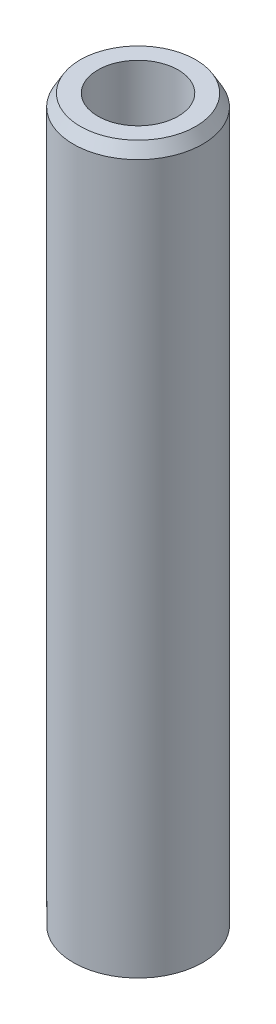
SolidWorks part; units mm, degrees
ref_plane "Front Plane" through (0, 0, 0) normal (0, 0, 1) x (1, 0, 0)
ref_plane "Top Plane" through (0, 0, 0) normal (0, 1, 0) x (1, 0, 0)
ref_plane "Right Plane" through (0, 0, 0) normal (1, 0, 0) x (0, 0, -1)
sketch "Sketch1" plane through (0, 0, 0) normal (0, 1, 0) x (1, 0, 0)
  circle A0 centre (0, 0) radius 25
  dimension "SHAFT_OD" = 50
extrude "Boss-Extrude1" add sketch "Sketch1" along normal blind 281.2914
sketch "Sketch2" plane through (0, 0, 0) normal (0, 1, 0) x (1, 0, 0)
  circle A0 centre (0, 0) radius 15.5245
  dimension "BORE_D" = 31.049
extrude "Cut-Extrude1" cut sketch "Sketch2" along normal through all
chamfer "Chamfer1" distance 4.628 angle 30 2 edges at (0, 281.2914, 25) (0, 0, 25) first distance on face at (0, 281.2914, 25) first distance on face at (0, 0, 15.5245)
